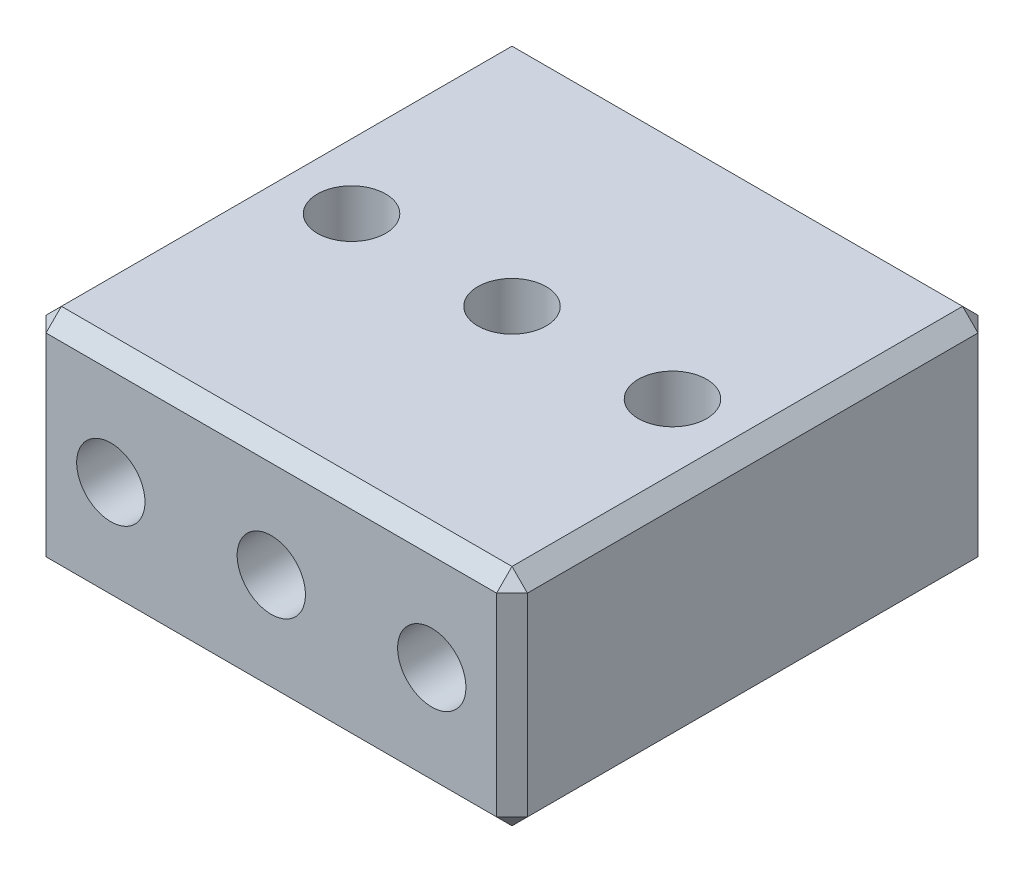
SolidWorks part; units mm, degrees
material "PET"
ref_plane "Front" through (0, 0, 0) normal (0, 0, 1) x (1, 0, 0)
ref_plane "Top" through (0, 0, 0) normal (0, 1, 0) x (1, 0, 0)
ref_plane "Right" through (0, 0, 0) normal (1, 0, 0) x (0, 0, -1)
sketch "Sketch1" plane through (0, 0, 0) normal (1, 0, 0) x (0, 0, -1)
  line L1 (23.8125, -11.1125) -> (-23.8125, -11.1125)
  line L2 (23.8125, -11.1125) -> (23.8125, 11.1125)
  line L3 (23.8125, 11.1125) -> (-23.8125, 11.1125)
  line L4 (-23.8125, -11.1125) -> (-23.8125, 11.1125)
  line L5 (23.8125, -11.1125) -> (-23.8125, 11.1125) construction
  line L6 (23.8125, 11.1125) -> (-23.8125, -11.1125) construction
  point P0 (0, 0)
  dimension "D1" = 22.225
  dimension "D2" = 47.625
extrude "Boss-Extrude1" add sketch "Sketch1" along normal mid plane 47.625
hole_wizard "1/4 Clearance Hole1" positions "Sketch2" profile "Sketch3" hole size "1/4" standard "ANSI Inch" end condition through all
sketch "Sketch2" plane through (0, 0, 23.8125) normal (0, 0, 1) x (1, 0, 0)
  line L0 (-15.875, 0) -> (15.875, 0) construction
  point P0 (0, 0)
  point P3 (-15.875, 0)
  point P5 (15.875, 0)
  dimension "D1" = 15.875
sketch "Sketch3" plane through (0, 0, 23.8125) normal (1, 0, 0) x (0, -1, 0)
  line L0 (0, 0) -> (0, 47.625)
  line L1 (0, 47.625) -> (3.3782, 47.625)
  line L2 (3.3782, 47.625) -> (3.3782, 0)
  line L5 (3.3782, 0) -> (0, 0)
  line L11 (0, -6.35) -> (0, 107.95) construction
  dimension "Thru Hole Dia." = 6.7564
  dimension "Thru Hole Depth" = 47.625
hole_wizard "1/4 Clearance Hole2" positions "Sketch4" profile "Sketch5" hole size "1/4" standard "ANSI Inch" end condition through all
sketch "Sketch4" plane through (0, 11.1125, 0) normal (0, 1, 0) x (1, 0, 0)
  line L0 (-15.875, 0) -> (15.875, 0) construction
  point P1 (-15.875, 0)
  point P2 (15.875, 0)
  point P8 (0, 0)
  dimension "D1" = 15.875
sketch "Sketch5" plane through (-15.875, 11.1125, 0) normal (1, 0, 0) x (0, 0, 1)
  line L0 (0, 0) -> (0, 22.225)
  line L1 (0, 22.225) -> (3.3782, 22.225)
  line L2 (3.3782, 22.225) -> (3.3782, 0)
  line L5 (3.3782, 0) -> (0, 0)
  line L11 (0, -6.35) -> (0, 107.95) construction
  dimension "Thru Hole Dia." = 6.7564
  dimension "Thru Hole Depth" = 22.225
chamfer "Chamfer1" distance 1.524 angle 45 12 edges at (-23.8125, -11.1125, 0) (0, -11.1125, -23.8125) (-23.8125, 0, -23.8125) (0, 11.1125, -23.8125) (-23.8125, 11.1125, 0) (-23.8125, 0, 23.8125) (0, -11.1125, 23.8125) (23.8125, 0, -23.8125) (23.8125, -11.1125, 0) (23.8125, 11.1125, 0) (23.8125, 0, 23.8125) (0, 11.1125, 23.8125)
